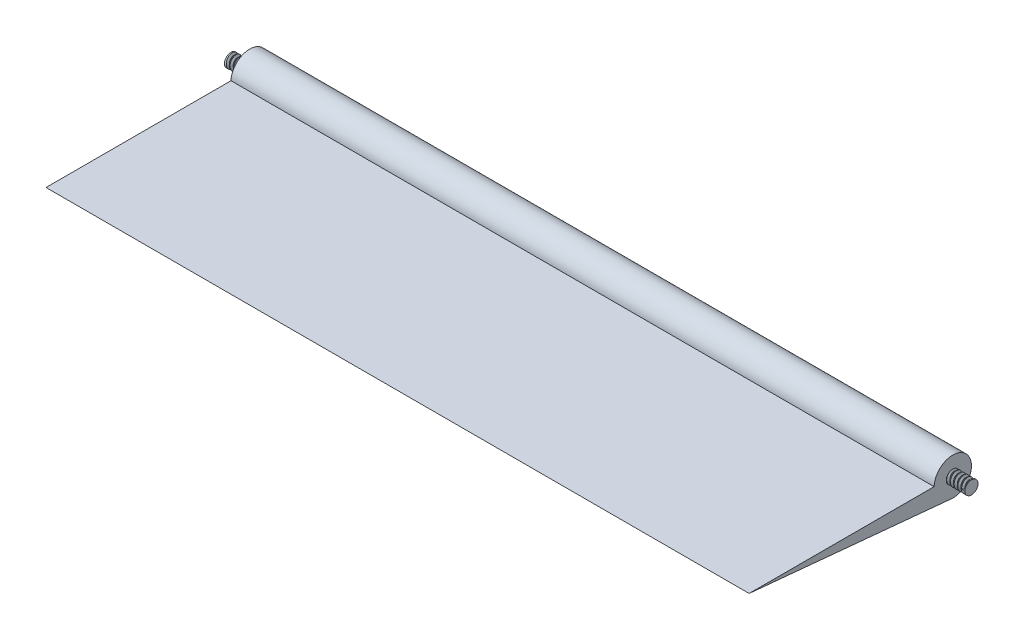
SolidWorks part; units mm, degrees
material "PET"
ref_plane "Front Plane" through (0, 0, 0) normal (0, 0, 1) x (1, 0, 0)
ref_plane "Top Plane" through (0, 0, 0) normal (0, 1, 0) x (1, 0, 0)
ref_plane "Right Plane" through (0, 0, 0) normal (1, 0, 0) x (0, 0, -1)
sketch "Sketch2" plane through (0, 0, 0) normal (1, 0, 0) x (0, 0, -1)
  line L10 (-138.43, 0.4249) -> (-12.6929, 0.4249)
  line L11 (-138.43, 0.4249) -> (0, -12.7)
  circle A0 centre (0, 0) radius 6.35
  arc A2 (0, 12.7) -> (0, -12.7) centre (0, 0) cw
  arc A3 (0, 12.7) -> (-12.6929, 0.4249) centre (0, 0) ccw
  dimension "D1" = 25.4
  dimension "D2" = 12.7
  dimension "D3" = 138.43
extrude "Boss-Extrude2" add sketch "Sketch2" along normal blind 477.9518
ref_plane "Plane1" through (238.9759, 0, 0) normal (-1, 0, 0) x (0, 0, 1)
sketch "Sketch3" plane through (238.9759, 0, 0) normal (-1, 0, 0) x (0, 0, 1)
  circle A0 centre (0, 0) radius 12.7
  dimension "D1" = 25.4
extrude "Boss-Extrude3" add sketch "Sketch3" along normal up to surface (238.9759 mm away) and the other way up to surface (238.9759 mm away) up to face at (0, 1.0387, 45.2157) other way up to face at (477.9518, 1.0387, 45.2157)
sketch "Sketch4" plane through (0, 0, 0) normal (-1, 0, 0) x (0, 0, 1)
  circle A0 centre (0, 0) radius 4.445
  point P3 (0, 0)
  dimension "D1" = 8.89
extrude "Boss-Extrude4" add sketch "Sketch4" along normal blind 12.7
thread "Thread1" pitch 2.54 method cut profile "Thread Profile1" start angle 0, offset 0, length 0, pitch 2.54, diameter 8.89
ref_plane "Plane2" through (-12.7, 0, -4.445) normal (0, -1, 0) x (0, 0, -1)
sketch "Thread Profile1" plane through (-12.7, 0, -4.445) normal (0, -1, 0) x (0, 0, -1)
  line L0 (0, 0) -> (0, 2.54) construction
  line L11 (0, 0) -> (0, 2.2225)
  line L12 (0, 2.2225) -> (-1.3748, 1.4287)
  line L13 (-1.3748, 1.4287) -> (-1.3748, 0.7937)
  line L15 (-1.3748, 0.7937) -> (0, 0)
  line L17 (-1.3748, 1.1112) -> (0, 1.1112) construction
  point P2 (0, 0)
  dimension "Pitch" = 2.54
  dimension "Profile_Angle" = 60
  dimension "Profile_Land" = 0.635
  dimension "Profile_Height" = 1.3748
mirror "Mirror3" about plane through (238.9759, 0, 0) normal (-1, 0, 0) of "Boss-Extrude4"
thread "Thread2" pitch 2.54 method cut profile "Thread Profile2" start angle 0, offset 0, length 0, pitch 2.54, diameter 8.89
ref_plane "Plane3" through (490.6518, 0, 4.445) normal (0, -1, 0) x (0, 0, 1)
sketch "Thread Profile2" plane through (490.6518, 0, 4.445) normal (0, -1, 0) x (0, 0, 1)
  line L0 (0, 0) -> (0, 2.54) construction
  line L11 (0, 0) -> (0, 2.2225)
  line L12 (0, 2.2225) -> (-1.3748, 1.4287)
  line L13 (-1.3748, 1.4287) -> (-1.3748, 0.7937)
  line L15 (-1.3748, 0.7937) -> (0, 0)
  line L17 (-1.3748, 1.1112) -> (0, 1.1112) construction
  point P2 (0, 0)
  dimension "Pitch" = 2.54
  dimension "Profile_Angle" = 60
  dimension "Profile_Land" = 0.635
  dimension "Profile_Height" = 1.3748
